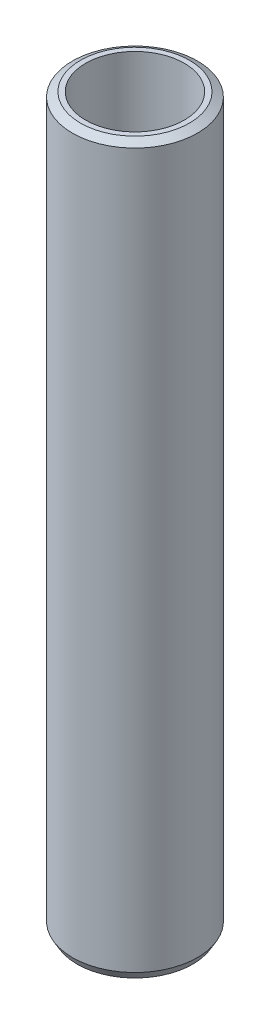
SolidWorks part; units mm, degrees
ref_plane "Front Plane" through (0, 0, 0) normal (0, 0, 1) x (1, 0, 0)
ref_plane "Top Plane" through (0, 0, 0) normal (0, 1, 0) x (1, 0, 0)
ref_plane "Right Plane" through (0, 0, 0) normal (1, 0, 0) x (0, 0, -1)
sketch "Sketch1" plane through (0, 0, 0) normal (0, 1, 0) x (1, 0, 0)
  circle A0 centre (0, 0) radius 37.5
  dimension "SHAFT_OD" = 75
extrude "Boss-Extrude1" add sketch "Sketch1" along normal blind 435.7518
sketch "Sketch2" plane through (0, 0, 0) normal (0, 1, 0) x (1, 0, 0)
  circle A0 centre (0, 0) radius 29.5752
  dimension "BORE_D" = 59.1505
extrude "Cut-Extrude1" cut sketch "Sketch2" along normal through all
chamfer "Chamfer1" distance 2.7878 angle 60 2 edges at (0, 435.7518, 37.5) (0, 0, 37.5) first distance on face at (0, 435.7518, 37.5) first distance on face at (0, 0, 29.5752)
